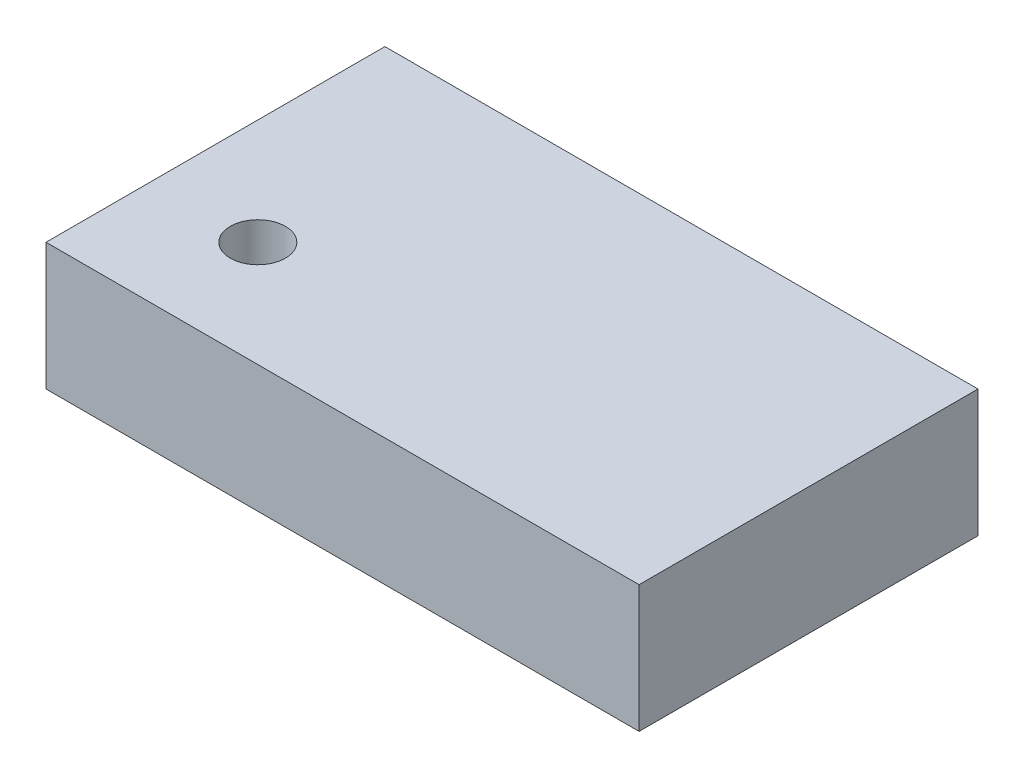
SolidWorks part; units mm, degrees
ref_plane "Front Plane" through (0, 0, 0) normal (0, 0, 1) x (1, 0, 0)
ref_plane "Top Plane" through (0, 0, 0) normal (0, 1, 0) x (1, 0, 0)
ref_plane "Right Plane" through (0, 0, 0) normal (1, 0, 0) x (0, 0, -1)
sketch "Sketch1" plane through (0, 0, 0) normal (0, 0, 1) x (1, 0, 0)
  line L1 (-45.1303, 23.1413) -> (94.8697, 23.1413)
  line L2 (-45.1303, 23.1413) -> (-45.1303, -6.8587)
  line L3 (-45.1303, -6.8587) -> (94.8697, -6.8587)
  line L4 (94.8697, 23.1413) -> (94.8697, -6.8587)
  dimension "D1" = 140
  dimension "D2" = 30
extrude "Boss-Extrude1" add sketch "Sketch1" along normal blind 80
sketch "Sketch2" plane through (0, 0, 0) normal (0, 0, -1) x (-1, 0, 0)
  line L0 (45.1303, -6.8587) -> (-94.8697, -6.8587) construction
  line L1 (45.1303, 23.1413) -> (45.1303, -6.8587) construction
  circle A0 centre (30.1303, 7.8145) radius 4.1759
  dimension "D1" = 14.6732
  dimension "D2" = 15
extrude "Cut-Extrude1" cut sketch "Sketch2" against normal blind 15
pattern_linear "LPattern1" count 4 spacing 110 along (1, 0, 0) of "Cut-Extrude1"
sketch "Sketch3" plane through (0, 23.1413, 0) normal (0, 1, 0) x (1, 0, 0)
  line L0 (94.8697, -80) -> (-45.1303, -80) construction
  line L1 (-45.1303, -80) -> (-45.1303, 0) construction
  circle A0 centre (-20.1303, -55) radius 6.5156
  dimension "D1" = 25
  dimension "D2" = 25
extrude "Cut-Extrude2" cut sketch "Sketch3" against normal blind 15
